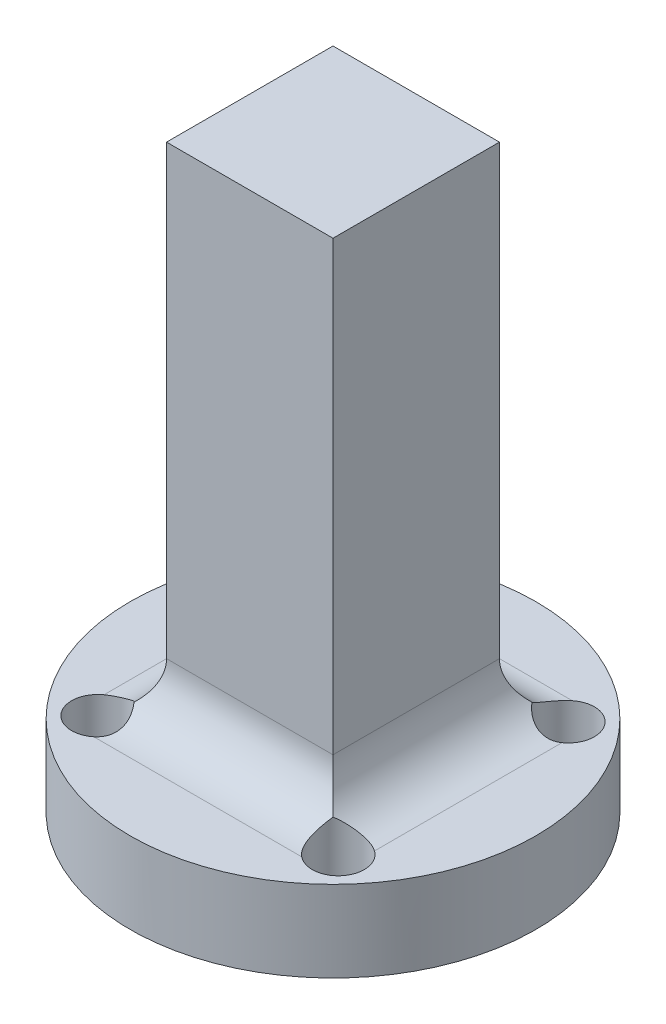
SolidWorks part; units mm, degrees
ref_plane "Front Plane" through (0, 0, 0) normal (0, 0, 1) x (1, 0, 0)
ref_plane "Top Plane" through (0, 0, 0) normal (0, 1, 0) x (1, 0, 0)
ref_plane "Right Plane" through (0, 0, 0) normal (1, 0, 0) x (0, 0, -1)
sketch "Sketch1" plane through (0, 0, 0) normal (0, 1, 0) x (1, 0, 0)
  line L1 (-5.7823, -5.5286) -> (5.7823, -5.5286)
  line L2 (-5.7823, -5.5286) -> (-5.7823, 5.5286)
  line L3 (-5.7823, 5.5286) -> (5.7823, 5.5286)
  line L4 (5.7823, -5.5286) -> (5.7823, 5.5286)
  line L5 (-5.7823, -5.5286) -> (5.7823, 5.5286) construction
  line L6 (-5.7823, 5.5286) -> (5.7823, -5.5286) construction
  circle A0 centre (0, 0) radius 9.75
  circle A1 centre (-5.7823, 5.5286) radius 1.25
  circle A2 centre (-5.7823, -5.5286) radius 1.25
  circle A3 centre (5.7823, -5.5286) radius 1.25
  circle A4 centre (5.7823, 5.5286) radius 1.25
  dimension "D1" = 19.5
  dimension "D3" = 2.5
  dimension "D4" = 2.5
  dimension "D5" = 2.5
  dimension "D6" = 2.5
  dimension "D2" = 16
extrude "Boss-Extrude2" add sketch "Sketch1" along normal blind 2 contours A0 A4 L4 A3 L1 A2 L2 A1 L3 | A4 L3 A1 L2 A2 L1 A3 L4 region at (0, 0, 0) region at (-9.4742, 0, 0)
sketch "Sketch2" plane through (0, 2, 0) normal (0, 1, 0) x (1, 0, 0)
  line L1 (-4, 4) -> (4, 4)
  line L2 (-4, 4) -> (-4, -4)
  line L3 (-4, -4) -> (4, -4)
  line L4 (4, 4) -> (4, -4)
  line L5 (-4, 4) -> (4, -4) construction
  line L6 (-4, -4) -> (4, 4) construction
  circle A0 centre (0, 0) radius 6.25
  dimension "D1" = 12.5
  dimension "D2" = 8
  dimension "D3" = 8
extrude "Boss-Extrude3" add sketch "Sketch2" along normal blind 24 contours L3 A0 L4 L1 L2 | L1 L4 L3 L2 region at (0, 2, 0)
sketch "Sketch7" plane through (0, 0, 0) normal (0, -1, 0) x (1, 0, 0)
  circle A4 centre (0, 0) radius 9.75
  circle A5 centre (0, 0) radius 4.5
  circle A6 centre (-5.7823, 5.5286) radius 1.25
  circle A7 centre (5.7823, 5.5286) radius 1.25
  circle A8 centre (5.7823, -5.5286) radius 1.25
  circle A9 centre (-5.7823, -5.5286) radius 1.25
  point P0 (0, 0)
  dimension "D1" = 9
  dimension "D2" = 19.5
extrude "Boss-Extrude5" add sketch "Sketch7" along normal blind 1.9
fillet "Fillet1" radius 2.5 4 edges at (0, 2, -4) (4, 2, 0) (0, 2, 4) (-4, 2, 0)
